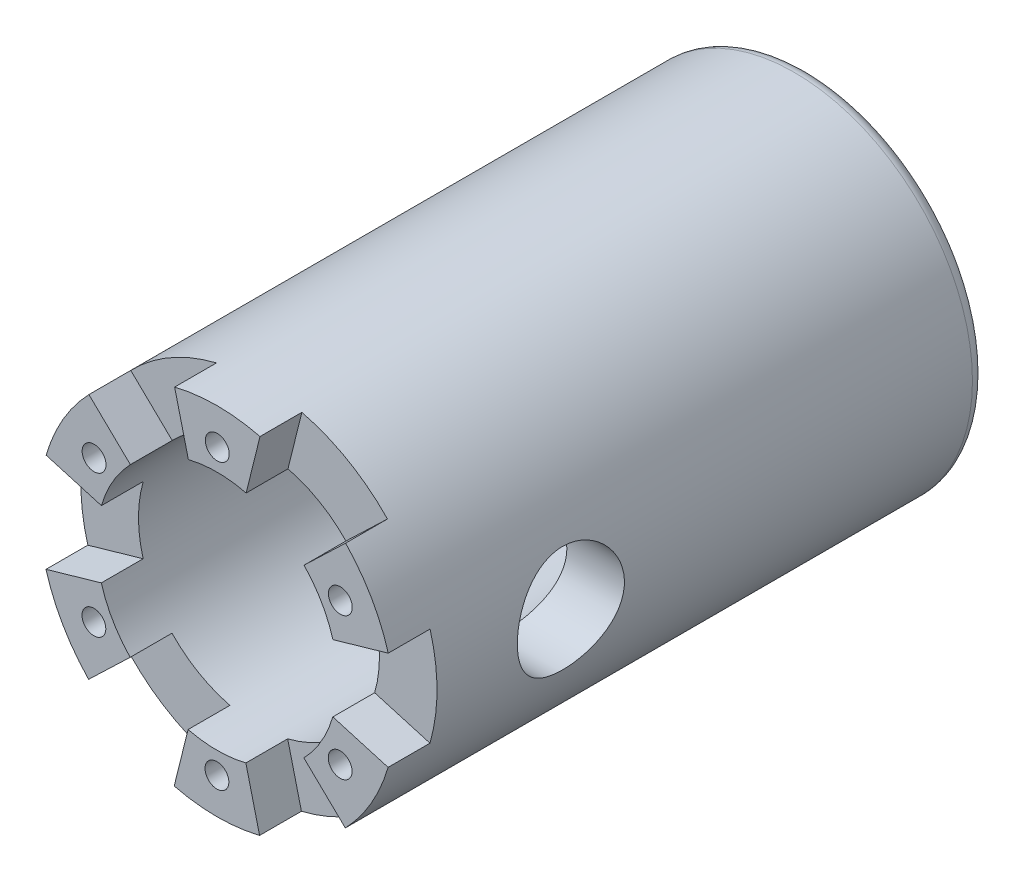
SolidWorks part; units mm, degrees
note: The reader was unsure of these and kept them because the rebuilt part matched: shared geometry of "Sketch11<4>".
material "ABS PC"
ref_plane "Front Plane" through (0, 0, 0) normal (0, 0, 1) x (1, 0, 0)
ref_plane "Top Plane" through (0, 0, 0) normal (0, 1, 0) x (1, 0, 0)
ref_plane "Right Plane" through (0, 0, 0) normal (1, 0, 0) x (0, 0, -1)
sketch "Sketch1" plane through (0, 0, 0) normal (0, 0, 1) x (1, 0, 0)
  circle A0 centre (0, 0) radius 16.891
  dimension "D1" = 33.782
extrude "Boss-Extrude1" add sketch "Sketch1" along normal blind 56.0324
sketch "Sketch9" plane through (0, 0, 0) normal (0, 0, -1) x (-1, 0, 0)
  line L0 (0, 0) -> (7.874, 0) construction
  line L1 (0, 0) -> (0, 7.874) construction
  line L2 (7.874, -7.874) -> (7.874, 7.874)
  line L3 (7.874, 7.874) -> (-7.874, 7.874)
  line L4 (-7.874, -7.874) -> (-7.874, 7.874)
  line L5 (7.874, -7.874) -> (-7.874, -7.874)
  circle A0 centre (0, 0) radius 9.525
  point P8 (-7.874, 0)
  dimension "D3" = 19.05
  dimension "D1" = 7.874
  dimension "D2" = 7.874
extrude "Cut-Extrude6" cut sketch "Sketch9" against normal through all contours A0 | L5 A0 | L4 A0 | L3 A0 | L2 A0
sketch "Sketch10" plane through (0, 0, 0) normal (0, 0, -1) x (-1, 0, 0)
  line L0 (-16.891, 0) -> (-11.43, 0) construction
  circle A0 centre (0, 0) radius 16.891
  circle A1 centre (0, 0) radius 11.43
  dimension "D1" = 22.86
  dimension "D2" = 33.782
extrude "Boss-Extrude2" add sketch "Sketch10" against normal blind 19.05
sketch "Sketch11" plane through (0, 0, 56.0324) normal (0, 0, 1) x (1, 0, 0)
  line L0 (-10.9842, -3.1612) -> (-16.2322, -4.6715)
  line L1 (-10.9762, 3.1888) -> (-16.2203, 4.7124)
  line L2 (-10.9762, 3.1888) -> (0, 0) construction
  line L3 (-10.9842, -3.1612) -> (0, 0) construction
  line L4 (-10.9762, 3.1888) -> (0, 0)
  line L5 (0, 0) -> (-10.9842, -3.1612)
  line L6 (0, 0) -> (-11.6719, 6.7584) construction
  line L7 (0, 0) -> (-16.9257, 0.0213) construction
  arc A2 (-10.9842, -3.1612) -> (-10.9762, 3.1888) centre (4.7575, -0.006) cw
  arc A3 (-16.2203, 4.7124) -> (-16.2322, -4.6715) centre (-0.84, 0.0011) ccw
  circle A4 centre (0, 0) radius 11.43
  circle M7 centre (0, 0) radius 16.891
  circle M33 centre (0, 0) radius 9.525
  dimension "D1" = 6.35
  dimension "D2" = 30
  dimension "D3" = 13.4874
extrude "Cut-Extrude7" cut sketch "Sketch11" against normal offset from surface (52.0636 mm away) 3.9688 contours L5 A4 L4 M33 | A2 L5 L4 M33 | A2 A4 up to face at (16.891, 0, 0)
extrude "Cut-Extrude8" cut sketch "Sketch11<4>" against normal blind 3.9688 contours A4 L1 L0 M7
sketch "Sketch11<4>" plane through (0, 0, 56.0324) normal (0, 0, 1) x (1, 0, 0) same geometry as "Sketch11"
hole_wizard "CSK for #2 Flat Head Machine Screw1" positions "Sketch13" profile "Sketch14" countersink size "#2" standard "ANSI Inch" end condition through all
sketch "Sketch13" plane through (0, 0, 0) normal (0, 0, -1) x (-1, 0, 0)
  point P0 (11.6719, 6.7584)
sketch "Sketch14" plane through (-11.6719, 6.7584, 0) normal (1, 0, 0) x (0, 1, 0)
  line L0 (0, 0) -> (0, 56.0324)
  line L1 (0, 56.0324) -> (1.1303, 56.0324)
  line L2 (1.1303, 56.0324) -> (1.1303, 1.2126)
  line L3 (1.1303, 1.2126) -> (2.1844, 0)
  line L5 (2.1844, 0) -> (0, 0)
  line L6 (-1.1303, 1.2126) -> (-2.1844, 0) construction
  line L11 (0, -6.35) -> (0, 107.95) construction
  dimension "Thru Hole Dia." = 2.2606
  dimension "Thru Hole Depth" = 56.0324
  dimension "Near C'Sink Dia." = 4.3688
  dimension "Near C'Sink Angle" = 82
pattern_circular "CirPattern1" count 6 over 360 about axis through (0, 0, 0) along (0, 0, 1) of "Cut-Extrude8", "CSK for #2 Flat Head Machine Screw1"
hole_wizard "1/2 (0.4) Diameter Hole1" positions "3DSketch1" profile "Sketch15" hole size "1/2" standard "ANSI Inch"
sketch3d "3DSketch1"
  line L0 (16.2322, 4.6715, 52.0636) -> (16.2203, -4.7124, 52.0636) construction
  line L2 (16.2262, -0.0204, 52.0636) -> (16.891, -0.0212, 52.0636) construction
  line L4 (16.891, -0.0212, 52.0636) -> (16.891, -0.0212, 0) construction
  line L6 (11.6889, 6.729, 0) -> (11.6719, -6.7584, 0) construction
  line L7 (11.6889, 6.729, 0) -> (11.6889, 6.729, 1.2126) construction
  line L8 (11.6719, -6.7584, 0) -> (11.6719, -6.7584, 1.2126) construction
  line L11 (11.6804, -0.0147, 0) -> (16.891, -0.0212, 0) construction
  circle A1 centre (0, 0, 0) radius 16.891 construction
  arc A2 (16.2203, -4.7124, 52.0636) -> (16.2322, 4.6715, 52.0636) centre (0, 0, 52.0636) ccw construction
  point P0 (16.891, -0.0212, 39.3636)
  point P19 (0, 0, 16.891)
  point P35 (0, 0, 68.9546)
  dimension "D1" = 12.7
sketch "Sketch15" plane through (16.891, -0.0212, 39.3636) normal (0, 0, 1) x (0.0013, 1, 0)
  line L0 (0, 0) -> (0, 15.7524)
  line L1 (0, 15.7524) -> (5.08, 12.7)
  line L2 (5.08, 12.7) -> (5.08, 0)
  line L5 (5.08, 0) -> (0, 0)
  line L10 (0, 15.7524) -> (-5.08, 12.7) construction
  line L11 (0, -6.35) -> (0, 107.95) construction
  dimension "Hole Dia." = 10.16
  dimension "Hole Depth" = 12.7
  dimension "Drill Angle" = 118
fillet "Fillet1" radius 1.27 1 edges at (16.891, 0, 0)
sketch "Sketch17" plane through (0, 0, 0) normal (0, 0, -1) x (-1, 0, 0)
  line L0 (8.238, 0.0197) -> (15.621, 0.0197) construction
  line L1 (8.238, 8.2747) -> (-8.272, 8.2747)
  line L2 (8.238, 8.2747) -> (8.238, -8.2353)
  line L3 (8.238, -8.2353) -> (-8.272, -8.2353)
  line L4 (-8.272, 8.2747) -> (-8.272, -8.2353)
  line L5 (-0.017, 8.2747) -> (-0.017, 13.4874) construction
  arc A0 (13.7824, -7.3526) -> (13.7638, 7.3873) centre (0, 0) ccw construction
  dimension "D1" = 16.51
  dimension "D2" = 16.51
extrude "Cut-Extrude9" cut sketch "Sketch17" against normal blind 12.7 from surface
